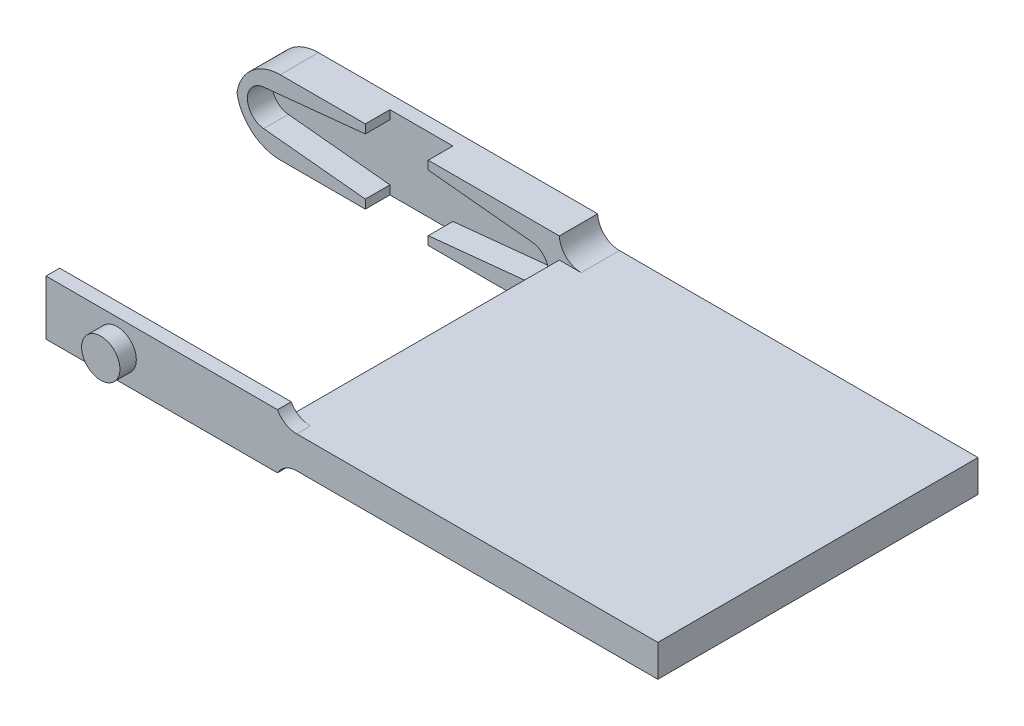
SolidWorks part; units mm, degrees
ref_plane "Front Plane" through (0, 0, 0) normal (0, 0, 1) x (1, 0, 0)
ref_plane "Top Plane" through (0, 0, 0) normal (0, 1, 0) x (1, 0, 0)
ref_plane "Right Plane" through (0, 0, 0) normal (1, 0, 0) x (0, 0, -1)
ref_plane "Ground Plane" through (0, 0, 29.25) normal (0, 0, -1) x (-1, 0, 0)
sketch "Sketch1" plane through (0, 0, 0) normal (0, 0, 1) x (1, 0, 0)
  line L0 (0, 3.375) -> (-13.75, 3.375) construction
  line L1 (0, 3.375) -> (0, 6.25) construction
  line L2 (-12.2651, 5.0167) -> (0, 6.25)
  line L3 (-13.75, 3.375) -> (-13.75, 1.1142) construction
  line L4 (-12.2651, 1.7333) -> (0, 0.5)
  line L5 (12.2651, 1.7333) -> (0, 0.5)
  line L6 (12.2651, 5.0167) -> (0, 6.25)
  line L7 (-2.875, 3.375) -> (-2.875, -5.5898) construction
  line L8 (-14.75, 0) -> (14.75, 0)
  line L9 (-14.75, 0) -> (-14.75, 6.75)
  line L10 (-14.75, 6.75) -> (14.75, 6.75)
  line L12 (13.75, 3.375) -> (13.75, 0.9067) construction
  line L13 (14.75, 4.8371) -> (49.5, 4.8371)
  line L14 (14.5, 4.8371) -> (14.5, 1.9129) construction
  line L15 (14.75, 1.9129) -> (49.5, 1.9129)
  line L16 (49.5, 4.8371) -> (49.5, 1.9129)
  line L18 (14.75, 6.75) -> (14.75, 0)
  circle A0 centre (0, 3.375) radius 2.875 construction
  arc A1 (-12.2651, 5.0167) -> (-12.2651, 1.7333) centre (-12.1, 3.375) ccw
  arc A2 (12.2651, 5.0167) -> (12.2651, 1.7333) centre (12.1, 3.375) cw
  circle A3 centre (-12.1, 3.375) radius 0.2914
  circle A4 centre (-10.0632, 3.375) radius 0.2914
  circle A5 centre (-8.0264, 3.375) radius 0.2914
  circle A6 centre (8.0264, 3.375) radius 0.2914
  circle A7 centre (10.0632, 3.375) radius 0.2914
  circle A8 centre (12.1, 3.375) radius 0.2914
  point P2 (-14.75, 3.375)
  point P27 (0, 6.75)
  point P34 (14.5, 3.375)
  point P35 (49.5, 3.375)
  dimension "D1" = 5.75
  dimension "D9" = 1.65
  dimension "D3" = 2.9241
  dimension "D5" = 29.5
  dimension "D7" = 6.75
  dimension "D8" = 1.7333
  dimension "D11" = 27.5
  dimension "D6" = 13.75
  dimension "D4" = 34.75
  dimension "D2" = 3
extrude "Boss-Extrude10" add sketch "Sketch1" along normal blind 3.5 contours L6 A2 L14 L10 L9 A1 L2 A0 | A2 L5 A0 L4 A1 L9 L8 region at (-14.4474, 3.375, 0)
extrude "Boss-Extrude15" add sketch "Sketch1<16>" along normal blind 1.25 contours A7 | A8 | A4 | A5 | A3 | L2 A1 L4 A0 A5 A4 A3 | L2 A0 L4 L5 L6 | A2 L6 A0 L5 A7 A6 A8 | A6 | A6 | L6 L2 A1 L4 L5 A2 region at (0, 3.375, 0) region at (-12.1, 3.375, 0) region at (-10.0632, 3.375, 0) region at (-8.0264, 3.375, 0) region at (8.0264, 3.375, 0) region at (10.0632, 3.375, 0) region at (12.1, 3.375, 0)
sketch "Sketch1<16>" plane through (0, 0, 0) normal (0, 0, 1) x (1, 0, 0) same geometry as "Sketch1"
extrude "Boss-Extrude17" add sketch "Sketch1<17>" along direction (0, 0, -1) on the side of the normal up to vertex (29.25 mm away) contours L13 L18 L15 L16 region at (32.125, 3.375, 0)
sketch "Sketch1<17>" plane through (0, 0, 0) normal (0, 0, 1) x (1, 0, 0) same geometry as "Sketch1"
sketch "Sketch2" plane through (0, 0, 29.25) normal (0, 0, 1) x (1, 0, 0)
  line L0 (14.75, 3.375) -> (-6.4, 3.375) construction
  line L1 (14.75, 4.8371) -> (49.5, 4.8371) construction
  line L2 (-6.4, 0.875) -> (14.75, 0.875)
  line L3 (-6.4, 5.875) -> (14.75, 5.875)
  line L4 (-6.4, 5.875) -> (-6.4, 0.875)
  line L5 (14.75, 5.875) -> (14.75, 0.875)
  line L6 (14.75, 4.8371) -> (14.75, 1.9129) construction
  dimension "D1" = 5
  dimension "D2" = 21.15
extrude "Boss-Extrude18" add sketch "Sketch2" against normal blind 1.25 contours L2 L5 L3 L4 | L4 L2 L5 L3 region at (4.175, 3.375, 29.25)
fillet "Fillet1" radius 2 4 edges at (14.75, 4.8371, 28.625) (14.75, 1.9129, 28.625)
fillet "Fillet2" radius 4 2 edges at (-14.75, 6.75, 1.75) (-14.75, 0, 1.75)
sketch "Sketch3" plane through (0, 0, 3.5) normal (0, 0, 1) x (1, 0, 0)
  line L0 (-0.1021, 0) -> (-0.1021, 6.75) construction
  line L1 (-2.9771, 6.75) -> (-2.9771, 0) construction
  line L3 (-10.75, 6.75) -> (14.75, 6.75) construction
  line L4 (-14.7009, 3.375) -> (-0.1021, 3.375) construction
  line L5 (2.7729, 6.75) -> (2.7729, 0) construction
  line L6 (2.7729, 6.75) -> (2.7729, 5.625)
  line L7 (-2.9771, 5.625) -> (2.7729, 5.625)
  line L8 (-2.9771, 0) -> (2.7729, 0)
  line L9 (-2.9771, 0) -> (-2.9771, 1.125)
  line L10 (-2.9771, 1.125) -> (2.7729, 1.125)
  line L11 (2.7729, 0) -> (2.7729, 1.125)
  line L12 (-2.9771, 6.75) -> (2.7729, 6.75)
  line L13 (-2.9771, 6.75) -> (-2.9771, 5.625)
  line L19 (-10.75, 0) -> (14.75, 0) construction
  circle A0 centre (-0.1021, 3.375) radius 2.875 construction
  circle A1 centre (-0.1021, 3.375) radius 2.875 construction
  circle A2 centre (-0.1021, 3.375) radius 2.25 construction
  circle A3 centre (-0.1021, 3.375) radius 2.25 construction
extrude "Cut-Extrude1" cut sketch "Sketch3" against normal up to surface (2.25 mm away)
sketch "Sketch4" plane through (0, 0, 29.25) normal (0, 0, 1) x (1, 0, 0)
  circle A0 centre (0.1021, 3.375) radius 1.75
  circle A1 centre (0.1021, 3.375) radius 2.25 construction
  circle A7 centre (0.1021, 3.375) radius 2.25
  dimension "D1" = 3.5
extrude "Boss-Extrude19" add sketch "Sketch4" along a picked direction on the side of the normal blind 1.5 contours A0
equation "\"D5@Sketch1\"=\"D6@Sketch1\"*2+2"
